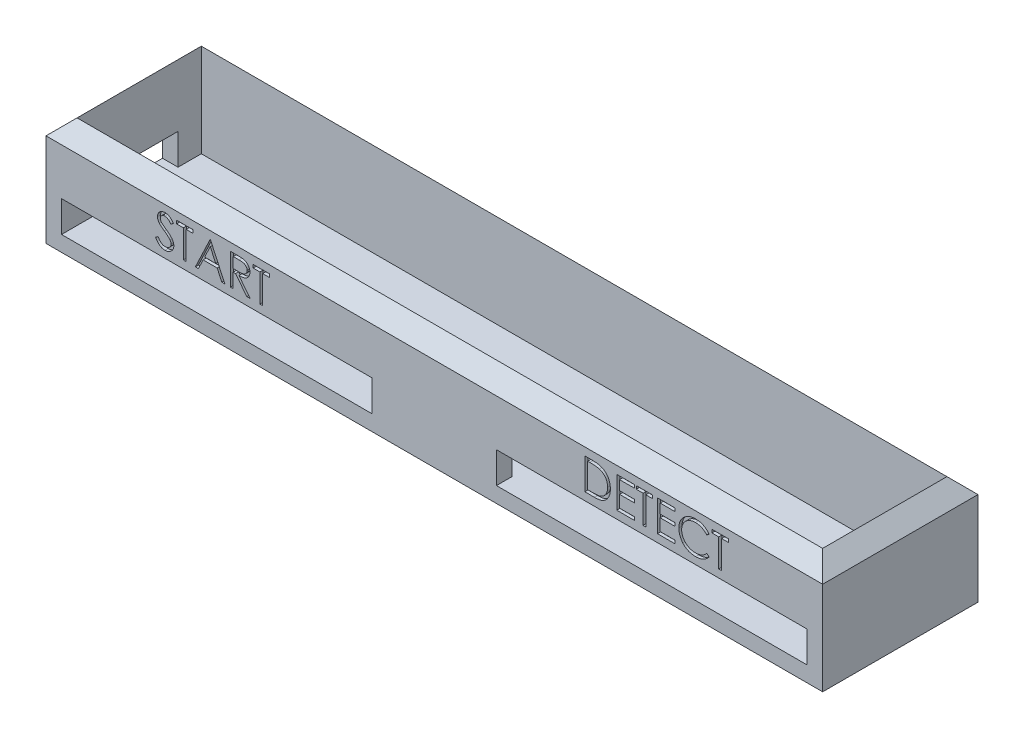
SolidWorks part; units mm, degrees
ref_plane "Front Plane" through (0, 0, 0) normal (0, 0, 1) x (1, 0, 0)
ref_plane "Top Plane" through (0, 0, 0) normal (0, 1, 0) x (1, 0, 0)
ref_plane "Right Plane" through (0, 0, 0) normal (1, 0, 0) x (0, 0, -1)
sketch "Sketch1" plane through (0, 0, 0) normal (0, 1, 0) x (1, 0, 0)
  line L1 (0, 0) -> (50, 0)
  line L2 (0, 0) -> (0, 10)
  line L3 (0, 10) -> (50, 10)
  line L4 (50, 0) -> (50, 10)
  dimension "D1" = 50
  dimension "D2" = 10
extrude "Boss-Extrude1" add sketch "Sketch1" along normal blind 8
shell "Shell1" thickness 1
sketch "Sketch2" plane through (0, 0, 0) normal (0, 0, 1) x (1, 0, 0)
  line L0 (0, 0) -> (50, 0) construction
  line L1 (1, 3) -> (21, 3)
  line L2 (1, 3) -> (1, 1)
  line L3 (1, 1) -> (21, 1)
  line L4 (21, 3) -> (21, 1)
  line L5 (0, 8) -> (0, 0) construction
  dimension "D1" = 20
  dimension "D2" = 2
  dimension "D3" = 1
  dimension "D4" = 1
extrude "Cut-Extrude1" cut sketch "Sketch2" against normal up to next
pattern_linear "LPattern3" count 2 spacing 28 along (1, 0, 0) of "Cut-Extrude1"
sketch "Sketch3" plane through (0, 0, 0) normal (-1, 0, 0) x (0, 0, 1)
  line L0 (-10, 0) -> (0, 0) construction
  line L1 (-7.5, 3) -> (-2.5, 3)
  line L2 (-7.5, 3) -> (-7.5, 1)
  line L3 (-7.5, 1) -> (-2.5, 1)
  line L4 (-2.5, 3) -> (-2.5, 1)
  line L5 (0, 8) -> (0, 0) construction
  dimension "D1" = 5
  dimension "D2" = 2
  dimension "D3" = 1
  dimension "D4" = 2.5
extrude "Arduino Cable" cut sketch "Sketch3" against normal up to next
sketch "Sketch4" plane through (0, 0, 0) normal (-1, 0, 0) x (0, 0, 1)
  line L0 (-10, 0) -> (0, 0) construction
  line L1 (-10, 8) -> (-10, 0) construction
  text T0 "MCU" font "Century Gothic" height 2
  dimension "D1" = 3.5
  dimension "D2" = 1.5
extrude "Arduino Deboss" cut sketch "Sketch4" against normal blind 0.2
sketch "Sketch5" plane through (0, 0, 0) normal (0, 0, 1) x (1, 0, 0)
  line L0 (0, 0) -> (50, 0) construction
  line L1 (0, 8) -> (0, 0) construction
  text T0 "START                          DETECT" font "Century Gothic" height 2
  dimension "D1" = 3.5
  dimension "D2" = 7
extrude "DB15 Labels" cut sketch "Sketch5" against normal blind 0.2
sketch "Sketch6" plane through (0, 8, 0) normal (0, 1, 0) x (1, 0, 0)
  line L1 (0, 10) -> (50, 10)
  line L2 (0, 10) -> (0, 0)
  line L3 (0, 0) -> (50, 0)
  line L4 (50, 10) -> (50, 0)
extrude "Cut-Extrude5" cut sketch "Sketch6" against normal blind 1
chamfer "Chamfer1" distance 1 angle 45 4 edges at (0, 7, -5) (25, 7, 0) (25, 7, -10) (50, 7, -5)
